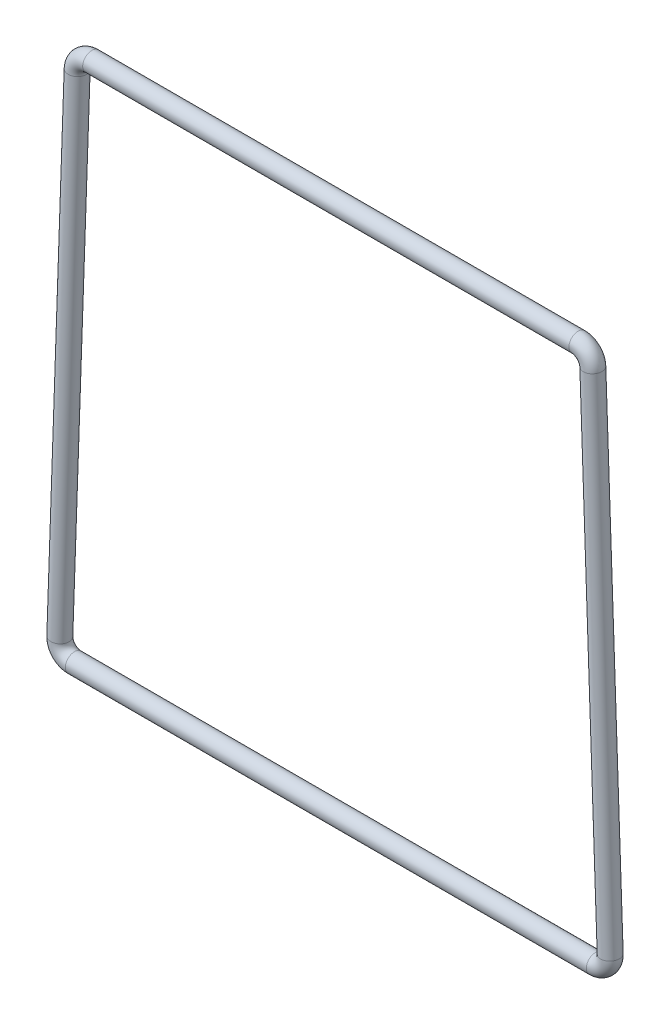
SolidWorks part; units mm, degrees
material "AISI 1035 Acero (SS)"
ref_plane "Alzado" through (0, 0, 0) normal (0, 0, 1) x (1, 0, 0)
ref_plane "Planta" through (0, 0, 0) normal (0, 1, 0) x (1, 0, 0)
ref_plane "Vista lateral" through (0, 0, 0) normal (1, 0, 0) x (0, 0, -1)
sketch "Croquis1" plane through (0, 0, 0) normal (0, 0, 1) x (1, 0, 0)
  line L0 (0, 0) -> (35.4294, 0)
  line L1 (37.4281, 2.0694) -> (35.067, 70.0694)
  line L2 (33.0682, 72) -> (0, 72)
  arc A0 (35.4294, 0) -> (37.4281, 2.0694) centre (35.4294, 2) ccw
  arc A1 (35.067, 70.0694) -> (33.0682, 72) centre (33.0682, 70) ccw
  point P9 (37.5, 0)
  point P12 (35, 72)
  dimension "D4" = 2
  dimension "D1" = 35
  dimension "D2" = 37.5
  dimension "D3" = 72
sketch "Croquis2" plane through (0, 0, 0) normal (1, 0, 0) x (0, 0, -1)
  line L0 (0, 2.0694) -> (0, 70.0694) construction
  circle A0 centre (0, 72) radius 1.25
  dimension "D1" = 2.5
sweep "Barrer1" add profiles "Croquis2" path "Croquis1"
mirror "Simetría1" about plane through (0, 72, 0) normal (1, 0, 0) of "Barrer1"
